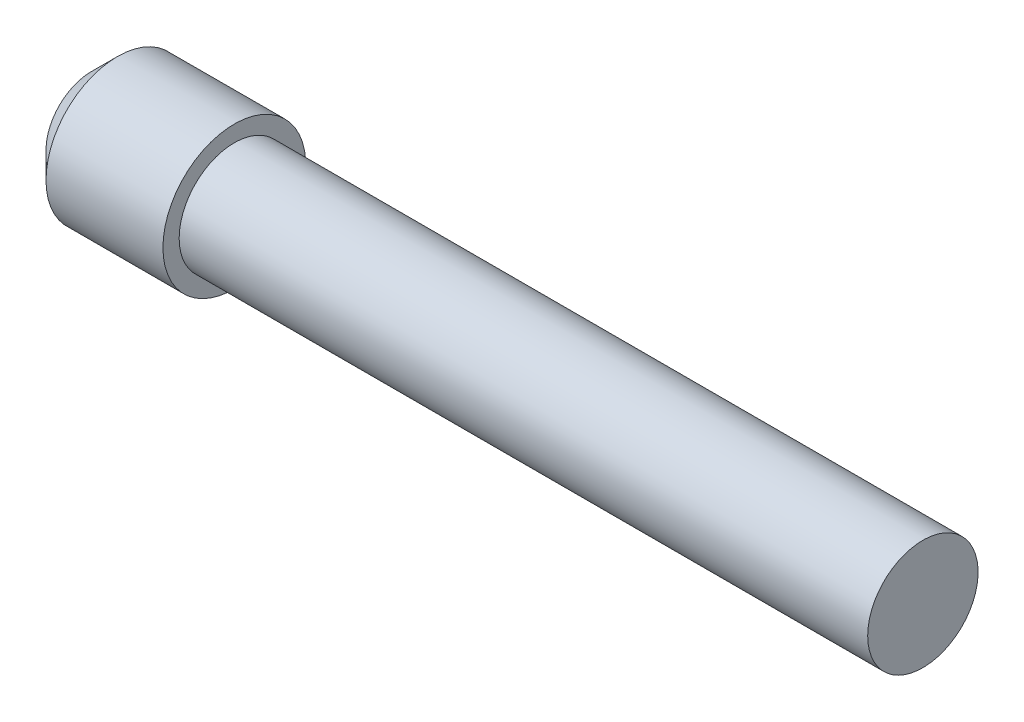
SolidWorks part; units mm, degrees
ref_plane "Front Plane" through (0, 0, 0) normal (0, 0, 1) x (1, 0, 0)
ref_plane "Top Plane" through (0, 0, 0) normal (0, 1, 0) x (1, 0, 0)
ref_plane "Right Plane" through (0, 0, 0) normal (1, 0, 0) x (0, 0, -1)
sketch "Sketch1" plane through (0, 0, 0) normal (0, 0, 1) x (1, 0, 0)
  line L0 (-9.4589, 0) -> (1.0894, 0) construction
  line L1 (0, 2.75) -> (-5.5, 2.75)
  line L2 (-5.5, 2.75) -> (-5.5, 0)
  line L3 (-5.5, 0) -> (26.5, 0)
  line L4 (0, 2.75) -> (0, 2.125)
  line L5 (0, 2.125) -> (0, 0) construction
  line L6 (0, 2.125) -> (26.5, 2.125)
  line L7 (26.5, 2.125) -> (26.5, 0)
  line L8 (9.5, 0) -> (9.5, 2.125) construction
  dimension "D1" = 9.5
  dimension "OD" = 5.5
  dimension "ID" = 4.25
  dimension "D2" = 17
  dimension "D3" = 5.5
revolve "Revolve1" add sketch "Sketch1" angle 360 about L0
ref_axis "Axis1" through (0, 0, 0) along (-1, 0, 0)
chamfer "Chamfer1" distance 1 angle 45 1 edges at (-5.5, 0, 2.75)
sketch "Sketch2" [suppressed] plane through (-5.5, 0, 0) normal (-1, 0, 0) x (0, 0, 1)
  circle A0 centre (0, 0) radius 4.75
  circle A1 centre (0, 0) radius 2.75 construction
  circle A2 centre (0, 0) radius 5.75
  dimension "D1" = 2
  dimension "D2" = 1
extrude "Boss-Extrude1" [suppressed] add sketch "Sketch2" against normal blind 30 separate body
sketch "Sketch3" [suppressed] plane through (0, 0, 0) normal (0, 0, 1) x (1, 0, 0)
  line L0 (-5.5, 2.75) -> (-5.5, -2.75) construction
  line L1 (-5.5, -0.8) -> (-4.7, -0.8)
  line L2 (-5.5, -0.8) -> (-5.5, 0.8)
  line L3 (-5.5, 0.8) -> (-4.7, 0.8)
  line L4 (-4.7, -0.8) -> (-4.7, 0.8)
  point P4 (-4.7, 0)
  dimension "D1" = 0.8
  dimension "D2" = 1.6
extrude "Boss-Extrude2" [suppressed] add sketch "Sketch3" along normal up to surface and the other way up to surface
pattern_circular "CirPattern1" [suppressed] count 4 over 360 reverse direction yes of bodies 103
pattern_linear "LPattern1" [suppressed] count 3 spacing 14.8 along (1, 0, 0) of bodies 104
